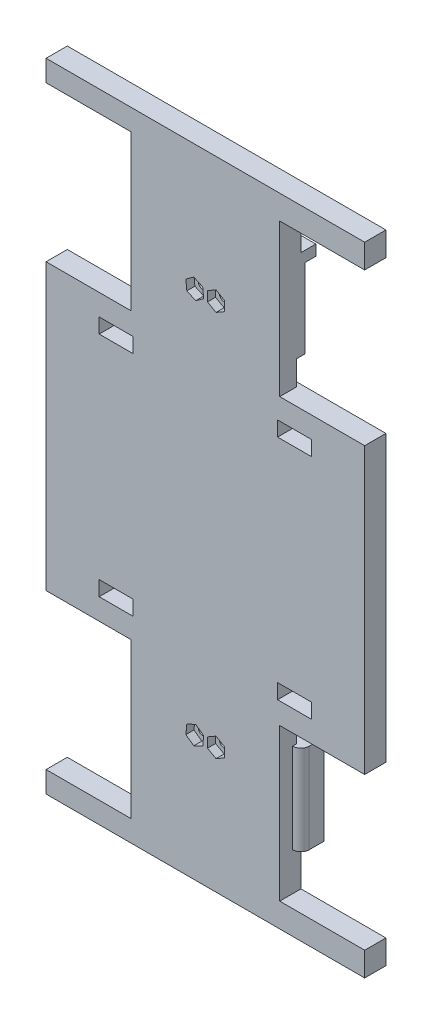
SolidWorks part; units mm, degrees
ref_plane "Front Plane" through (0, 0, 0) normal (0, 0, 1) x (1, 0, 0)
ref_plane "Top Plane" through (0, 0, 0) normal (0, 1, 0) x (1, 0, 0)
ref_plane "Right Plane" through (0, 0, 0) normal (1, 0, 0) x (0, 0, -1)
sketch "Sketch2" plane through (0, 0, 0) normal (0, 0, 1) x (1, 0, 0)
  line L0 (-180, 280) -> (-180, 200) construction
  line L1 (0, 0) -> (-150, 0)
  line L2 (0, 0) -> (0, 20)
  line L3 (0, 300) -> (-150, 300)
  line L4 (-150, 0) -> (-150, 20)
  line L5 (-180, 100) -> (-180, 20) construction
  line L6 (30, 280) -> (30, 200) construction
  line L7 (30, 100) -> (30, 20) construction
  line L8 (-180, 280) -> (-150, 280) construction
  line L9 (-180, 200) -> (-150, 200) construction
  line L10 (30, 280) -> (0, 280) construction
  line L11 (30, 200) -> (0, 200) construction
  line L12 (-180, 100) -> (-150, 100) construction
  line L13 (-180, 20) -> (-150, 20) construction
  line L14 (30, 100) -> (0, 100) construction
  line L15 (30, 20) -> (0, 20) construction
  line L16 (0, 280) -> (0, 300)
  line L17 (-150, 280) -> (-110, 280)
  line L19 (-150, 200) -> (-110, 200)
  line L20 (-110, 280) -> (-110, 200)
  line L21 (0, 280) -> (-40, 280)
  line L23 (0, 200) -> (-40, 200)
  line L24 (-40, 280) -> (-40, 200)
  line L25 (-150, 100) -> (-110, 100)
  line L27 (-150, 20) -> (-110, 20)
  line L28 (-110, 100) -> (-110, 20)
  line L29 (0, 100) -> (-40, 100)
  line L31 (0, 20) -> (-40, 20)
  line L32 (-40, 100) -> (-40, 20)
  line L33 (-150, 280) -> (-150, 300)
  line L34 (-150, 100) -> (-150, 200)
  line L35 (0, 100) -> (0, 200)
  dimension "D1" = 300
  dimension "D2" = 80
  dimension "D3" = 150
  dimension "D4" = 20
  dimension "D5" = 20
  dimension "D6" = 30
  dimension "D7" = 30
  dimension "D8" = 40
extrude "Boss-Extrude1" add sketch "Sketch2" along normal blind 10
sketch "Sketch3" plane through (0, 0, 0) normal (0, 0, -1) x (-1, 0, 0)
  line L0 (110, 20) -> (150, 20) construction
  line L5 (40, 100) -> (110, 100) construction
  line L22 (40, 100) -> (40, 85.9941) construction
  line L24 (40, 20) -> (110, 20) construction
  line L25 (110, 100) -> (110, 85.9941) construction
  line L29 (40, 60) -> (110, 60) construction
  line L30 (110, 34.6298) -> (110, 20) construction
  line L33 (40, 34.2339) -> (58.8, 34.2339)
  line L34 (58.8, 82.9565) -> (58.8, 34.2339)
  line L37 (110, 34.6298) -> (91.2, 34.6298)
  line L38 (91.2, 82.9565) -> (91.2, 34.6298)
  line L40 (40, 34.2339) -> (40, 29.2339)
  line L41 (40, 29.2339) -> (63.8, 29.2339)
  line L42 (63.8, 82.9565) -> (63.8, 29.2339)
  line L45 (110, 29.2339) -> (86.2, 29.2339)
  line L46 (86.2, 82.9565) -> (86.2, 29.2339)
  line L47 (110, 34.6298) -> (110, 29.2339)
  line L48 (58.8, 82.9565) -> (63.8, 82.9565)
  line L49 (91.2, 82.9565) -> (86.2, 82.9565)
  line L50 (40, 34.2339) -> (40, 20) construction
  line L51 (110, 100) -> (110, 20) construction
  dimension "D1" = 18.8
  dimension "D2" = 5
  dimension "D3" = 5
extrude "Boss-Extrude3" add sketch "Sketch3" along normal blind 7
sketch "Sketch4" plane through (0, 0, 0) normal (0, 0, -1) x (-1, 0, 0)
  line L1 (58.8, 82.9565) -> (40, 82.9565)
  line L2 (58.8, 82.9565) -> (58.8, 34.2339)
  line L3 (58.8, 34.2339) -> (40, 34.2339)
  line L4 (40, 82.9565) -> (40, 34.2339)
  line L5 (91.2, 82.9565) -> (110, 82.9565)
  line L6 (91.2, 82.9565) -> (91.2, 34.6298)
  line L7 (91.2, 34.6298) -> (110, 34.6298)
  line L8 (110, 82.9565) -> (110, 34.6298)
extrude "Boss-Extrude4" add sketch "Sketch4" along normal blind 2
sketch "Sketch5" plane through (0, 0, -2) normal (0, 0, -1) x (-1, 0, 0)
  line L0 (40, 82.9565) -> (40, 34.2339) construction
  line L1 (58.8, 82.9565) -> (40, 82.9565)
  line L2 (58.8, 82.9565) -> (58.8, 71.4798)
  line L3 (58.8, 71.4798) -> (40, 71.4798)
  line L4 (40, 82.9565) -> (40, 71.4798)
  line L5 (91.2, 34.6298) -> (91.2, 82.9565) construction
  line L6 (110, 82.9565) -> (91.2, 82.9565)
  line L7 (110, 82.9565) -> (110, 71.4798)
  line L8 (110, 71.4798) -> (91.2, 71.4798)
  line L9 (91.2, 82.9565) -> (91.2, 71.4798)
  dimension "D1" = 11.4766
sketch "Sketch6" plane through (0, 0, -7) normal (0, 0, -1) x (-1, 0, 0)
  line L0 (63.8, 29.2339) -> (63.8, 82.9565) construction
  line L1 (40, 82.9565) -> (55.1725, 82.9565)
  line L2 (40, 82.9565) -> (40, 71.4798)
  line L3 (40, 71.4798) -> (58.8, 71.4798)
  line L5 (91.2, 82.9565) -> (110, 82.9565)
  line L7 (95.4907, 71.4798) -> (110, 71.4798)
  line L8 (110, 82.9565) -> (110, 71.4798)
  line L9 (55.1725, 82.9565) -> (63.8, 82.9565)
  line L11 (58.8, 71.4798) -> (63.8, 71.4798)
  line L12 (63.8, 82.9565) -> (63.8, 71.4798)
  line L14 (86.2, 82.9565) -> (91.2, 82.9565)
  line L15 (86.2, 82.9565) -> (86.2, 71.4798)
  line L16 (86.2, 71.4798) -> (95.4907, 71.4798)
extrude "Cut-Extrude2" cut sketch "Sketch6" against normal blind 9
sketch "Sketch7" plane through (0, 0, 0) normal (0, 0, -1) x (-1, 0, 0)
  line L0 (40, 71.4798) -> (40, 34.2339) construction
  line L1 (150, 0) -> (0, 0) construction
  circle A0 centre (70, 59.0298) radius 2.165
  circle A1 centre (80, 59.0298) radius 2.165
  dimension "D4" = 4.33
  dimension "D1" = 30
  dimension "D2" = 10
  dimension "D3" = 59.0298
extrude "Cut-Extrude3" cut sketch "Sketch7" against normal through all
sketch "Sketch8" plane through (0, 0, 10) normal (0, 0, 1) x (1, 0, 0)
  line L1 (-83.7401, 61.7079) -> (-84.1893, 57.1299)
  line L2 (-84.1893, 57.1299) -> (-80.4492, 54.4518)
  line L3 (-80.4492, 54.4518) -> (-76.2599, 56.3518)
  line L4 (-76.2599, 56.3518) -> (-75.8107, 60.9298)
  line L5 (-75.8107, 60.9298) -> (-79.5508, 63.6078)
  line L6 (-79.5508, 63.6078) -> (-83.7401, 61.7079)
  line L7 (-70, 63.6298) -> (-73.9837, 61.3298)
  line L8 (-73.9837, 61.3298) -> (-73.9837, 56.7298)
  line L9 (-73.9837, 56.7298) -> (-70, 54.4298)
  line L10 (-70, 54.4298) -> (-66.0163, 56.7298)
  line L11 (-66.0163, 56.7298) -> (-66.0163, 61.3298)
  line L12 (-66.0163, 61.3298) -> (-70, 63.6298)
  circle A0 centre (-80, 59.0298) radius 3.9837 construction
  circle A1 centre (-70, 59.0298) radius 3.9837 construction
  dimension "D1" = 4.6
extrude "Cut-Extrude4" cut sketch "Sketch8" against normal blind 3.8
sketch "Sketch9" plane through (0, 29.2339, 0) normal (0, -1, 0) x (1, 0, 0)
  line L0 (-150, 0) -> (0, 0) construction
  line L1 (-110, -7) -> (-113.9, -7)
  line L2 (-110, -7) -> (-110, 0)
  line L4 (-113.9, -7) -> (-113.9, 0)
  line L5 (-110, 3.9) -> (-110, 0)
  line L6 (-40, -7) -> (-36.1, -7)
  line L7 (-40, -7) -> (-40, 0)
  line L9 (-36.1, -7) -> (-36.1, 0)
  line L12 (-40, 3.9) -> (-40, 0)
  arc A0 (-110, 3.9) -> (-113.9, 0) centre (-110, 0) ccw
  arc A2 (-36.1, 0) -> (-40, 3.9) centre (-40, 0) ccw
  dimension "D1" = 3.9
extrude "Boss-Extrude5" add sketch "Sketch9" against normal up to surface (42.2459 mm away) up to face at (-94.4286, 71.4798, -2)
ref_plane "Plane1" through (0, 150, 0) normal (0, 1, 0) x (1, 0, 0)
mirror "Mirror2" about plane through (0, 150, 0) normal (0, 1, 0) of "Cut-Extrude2", "Boss-Extrude3", "Boss-Extrude4"
mirror "Mirror3" about plane through (0, 150, 0) normal (0, 1, 0) of "Cut-Extrude3"
mirror "Mirror4" about plane through (0, 150, 0) normal (0, 1, 0) of "Cut-Extrude4"
sketch "Sketch10" plane through (0, 0, 0) normal (0, 0, -1) x (-1, 0, 0)
  line L2 (150, 300) -> (150, 280) construction
  line L3 (0, 288.6638) -> (40, 288.6638)
  line L4 (0, 288.6638) -> (0, 280)
  line L5 (0, 280) -> (40, 280)
  line L6 (40, 288.6638) -> (40, 280)
  line L7 (150, 290) -> (110, 290)
  line L8 (150, 290) -> (150, 280)
  line L9 (150, 280) -> (110, 280)
  line L10 (110, 290) -> (110, 280)
  dimension "D2" = 10
extrude "Cut-Extrude5" cut sketch "Sketch10" against normal through all
mirror "Mirror5" about plane through (0, 150, 0) normal (0, 1, 0) of "Cut-Extrude5"
sketch "Sketch11" plane through (0, 0, 0) normal (0, 0, -1) x (-1, 0, 0)
  line L0 (51.3081, 300) -> (51.3081, 254.1702) construction
  line L1 (0, 300) -> (150, 300) construction
  line L2 (110, 228.5202) -> (110, 217.0435) construction
  line L3 (0, 200) -> (40, 200)
  line L4 (0, 200) -> (0, 217.0435)
  line L5 (0, 217.0435) -> (40, 217.0435)
  line L6 (40, 200) -> (40, 217.0435)
  line L7 (110, 217.0435) -> (150, 217.0435)
  line L8 (110, 217.0435) -> (110, 200)
  line L9 (110, 200) -> (150, 200)
  line L10 (150, 217.0435) -> (150, 200)
  line L11 (0, 217.0435) -> (0, 262.8734) construction
  dimension "D1" = 45.8298
extrude "Boss-Extrude6" add sketch "Sketch11" against normal through all
mirror "Mirror6" about plane through (0, 150, 0) normal (0, 1, 0) of "Boss-Extrude6"
sketch "Sketch12" plane through (0, 0, 10) normal (0, 0, 1) x (1, 0, 0)
  line L0 (-150, 217.0435) -> (-110, 217.0435) construction
  line L1 (-125, 207.0435) -> (-109, 207.0435)
  line L2 (-125, 207.0435) -> (-125, 200.0435)
  line L3 (-125, 200.0435) -> (-109, 200.0435)
  line L4 (-109, 207.0435) -> (-109, 200.0435)
  line L5 (-25, 200.0435) -> (-41, 200.0435)
  line L6 (-25, 200.0435) -> (-25, 207.0435)
  line L7 (-25, 207.0435) -> (-41, 207.0435)
  line L8 (-41, 200.0435) -> (-41, 207.0435)
  line L9 (-125, 99.9565) -> (-109, 99.9565)
  line L10 (-125, 99.9565) -> (-125, 92.9565)
  line L11 (-125, 92.9565) -> (-109, 92.9565)
  line L12 (-109, 99.9565) -> (-109, 92.9565)
  line L13 (-41, 99.9565) -> (-25, 99.9565)
  line L14 (-41, 99.9565) -> (-41, 92.9565)
  line L15 (-41, 92.9565) -> (-25, 92.9565)
  line L16 (-25, 99.9565) -> (-25, 92.9565)
  line L17 (-150, 217.0435) -> (-150, 82.9565) construction
  line L18 (0, 82.9565) -> (0, 217.0435) construction
  line L19 (-150, 82.9565) -> (-110, 82.9565) construction
  dimension "D1" = 10
  dimension "D2" = 25
  dimension "D3" = 25
  dimension "D4" = 10
  dimension "D5" = 7
  dimension "D6" = 16
extrude "Cut-Extrude6" cut sketch "Sketch12" against normal up to next
